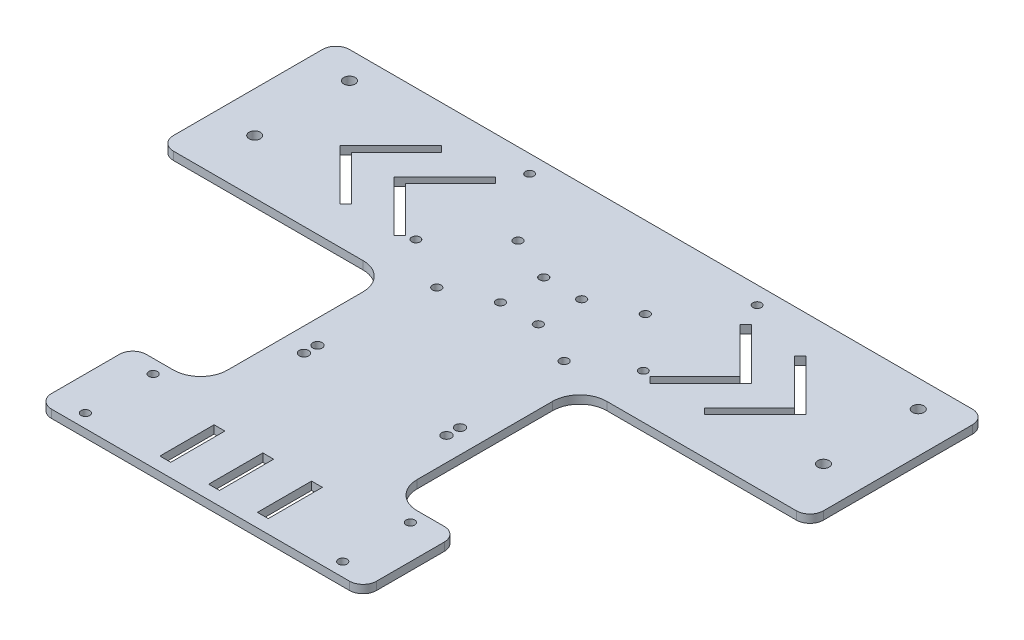
SolidWorks part; units mm, degrees
material "Thornel Mat VMA"
ref_plane "前视基准面" through (0, 0, 0) normal (0, 0, 1) x (1, 0, 0)
ref_plane "上视基准面" through (0, 0, 0) normal (0, 1, 0) x (1, 0, 0)
ref_plane "右视基准面" through (0, 0, 0) normal (1, 0, 0) x (0, 0, -1)
sketch "草图1" plane through (0, 0, 0) normal (0, 1, 0) x (1, 0, 0)
  line L0 (-105, 32.5) -> (-105, -32.5) construction
  line L1 (-120, -32.5) -> (120, -32.5)
  line L2 (-120, -32.5) -> (-120, 32.5)
  line L3 (-120, 32.5) -> (120, 32.5)
  line L4 (120, -32.5) -> (120, 32.5)
  line L5 (-120, -32.5) -> (120, 32.5) construction
  line L6 (-120, 32.5) -> (120, -32.5) construction
  line L7 (0, 32.5) -> (0, -32.5) construction
  line L8 (0, -82.5) -> (0, -32.5) construction
  line L9 (-60, -32.5) -> (20, -32.5)
  circle A0 centre (-105, 22.5) radius 2.1
  circle A1 centre (-105, -12.5) radius 2.1
  circle A2 centre (105, -12.5) radius 2.1
  circle A3 centre (105, 22.5) radius 2.1
  point P0 (0, 0)
  dimension "D4" = 20
  dimension "D5" = 35
  dimension "D1" = 65
  dimension "D2" = 240
  dimension "D3" = 15
extrude "凸台-拉伸1" add sketch "草图1" along normal blind 3 contours L1 L4 L3 L2 A2 A1 A0 A3 | L1 region at (0, 0, 0.0178)
sketch "草图3" plane through (0, 3, 0) normal (0, 1, 0) x (1, 0, 0)
  line L0 (0.7261, -44.1829) -> (0.7261, -109.1829) construction
  line L2 (-120, -32.5) -> (120, -32.5) construction
  line L3 (-40, -12.5) -> (40, -12.5) construction
  circle A0 centre (-22.7739, 2.5) radius 1.6
  circle A1 centre (24.2261, 2.5) radius 1.6
  circle A2 centre (24.2261, -27.5) radius 1.6
  circle A3 centre (-22.7739, -27.5) radius 1.6
  circle A4 centre (-6.2739, -4.5) radius 1.6
  circle A5 centre (7.7261, -4.5) radius 1.6
  circle A6 centre (7.7261, -20.5) radius 1.6
  circle A7 centre (-6.2739, -20.5) radius 1.6
  dimension "D1" = 3.2
  dimension "D2" = 47
  dimension "D3" = 30
  dimension "D4" = 14
  dimension "D5" = 16
  dimension "D6" = 5
extrude "切除-拉伸1" cut sketch "草图3" against normal through all
sketch "草图4" plane through (0, 0, 0) normal (0, 1, 0) x (1, 0, 0)
  line L0 (0, 32.5) -> (0, -113.7655) construction
  line L2 (-35, -32.5) -> (-35, -137.5)
  line L3 (-120, -32.5) -> (120, -32.5) construction
  line L4 (-35, -137.5) -> (35, -137.5)
  line L5 (35, -32.5) -> (35, -137.5)
  line L6 (-35, -32.5) -> (35, -32.5)
  line L7 (-35, -102.5) -> (-60, -102.5)
  line L8 (-60, -102.5) -> (-60, -137.5)
  line L9 (-60, -137.5) -> (-35, -137.5)
  line L10 (60, -102.5) -> (60, -137.5)
  line L11 (60, -137.5) -> (35, -137.5)
  line L12 (35, -102.5) -> (60, -102.5)
  point P9 (0, -137.5)
  dimension "D1" = 105
  dimension "D2" = 35
  dimension "D3" = 60
  dimension "D4" = 35
extrude "凸台-拉伸2" add sketch "草图4" along normal blind 3 contours L0 L6 L2 L4 | L6 L0 L4 L5 | L8 L9 L2 L7 | L12 L5 L11 L10 region at (-17.5, 0, 33.7619) region at (-47.5, 0, 120) region at (47.5, 0, 120)
fillet "圆角1" radius 10 2 edges at (35, 1.5, 32.5) (-35, 1.5, 32.5)
sketch "草图5" plane through (0, 3, 0) normal (0, 1, 0) x (1, 0, 0)
  line L0 (0, 32.5) -> (0, -137.5) construction
  line L1 (-120, 32.5) -> (120, 32.5) construction
  line L2 (-2, -112.5) -> (2, -112.5)
  line L3 (-120, -132.5) -> (120, -132.5) construction
  line L4 (-120, -32.5) -> (-120, 32.5) construction
  line L5 (120, -32.5) -> (120, 32.5) construction
  line L6 (-20, -112.5) -> (-16, -112.5)
  line L7 (-60, -137.5) -> (60, -137.5) construction
  line L8 (-20, -112.5) -> (-20, -132.5)
  line L9 (-20, -132.5) -> (-16, -132.5)
  line L10 (-16, -112.5) -> (-16, -132.5)
  line L11 (-2, -112.5) -> (-2, -132.5)
  line L12 (2, -112.5) -> (2, -132.5)
  line L13 (-2, -132.5) -> (2, -132.5)
  line L14 (16, -112.5) -> (20, -112.5)
  line L15 (16, -112.5) -> (16, -132.5)
  line L16 (20, -112.5) -> (20, -132.5)
  line L17 (16, -132.5) -> (20, -132.5)
  circle A0 centre (-47.5, -132.5) radius 1.6
  circle A1 centre (47.5, -132.5) radius 1.6
  circle A2 centre (-47.5, -107.5) radius 1.6
  circle A3 centre (47.5, -107.5) radius 1.6
  point P25 (-18, -112.5)
  point P33 (18, -112.5)
  dimension "D2" = 3.2
  dimension "D3" = 95
  dimension "D1" = 5
  dimension "D5" = 20
  dimension "D6" = 16
  dimension "D7" = 4
  dimension "D9" = 36
  dimension "D4" = 2
  dimension "D8" = 3
extrude "切除-拉伸2" cut sketch "草图5" against normal through all
fillet "圆角2" radius 10 2 edges at (35, 1.5, 102.5) (-35, 1.5, 102.5)
sketch "草图7" plane through (0, 3, 0) normal (0, 1, 0) x (1, 0, 0)
  line L0 (-120, 0) -> (120, 0) construction
  line L1 (-120, -32.5) -> (-120, 32.5) construction
  line L2 (120, -32.5) -> (120, 32.5) construction
  line L3 (0, 32.5) -> (0, -32.5) construction
  line L4 (-120, 32.5) -> (120, 32.5) construction
  line L5 (-105, 22.5) -> (-105, -12.5) construction
  line L6 (-22.7739, 2.5) -> (-22.7739, -27.5) construction
  line L7 (-22.7739, 2.5) -> (-105, 2.5) construction
  line L8 (-63.887, 2.5) -> (-63.887, 0) construction
  line L9 (-63.887, 0) -> (-46.2093, 17.6777)
  line L10 (-83.887, 0) -> (-66.2093, 17.6777)
  line L11 (-63.887, 0) -> (-46.2093, -17.6777)
  line L12 (-83.887, 0) -> (-66.2093, -17.6777)
  line L13 (83.887, 0) -> (66.2093, -17.6777)
  line L14 (63.887, 0) -> (46.2093, -17.6777)
  line L15 (63.887, 0) -> (46.2093, 17.6777)
  line L16 (83.887, 0) -> (66.2093, 17.6777)
  dimension "D1" = 25
  dimension "D2" = 45
  dimension "D3" = 2
extrude "切除-拉伸-薄壁1" cut sketch "草图7" against normal through all thin thin type mid plane wall 3
sketch "草图8" plane through (0, 3, 0) normal (0, 1, 0) x (1, 0, 0)
  line L0 (-35, -42.5) -> (35, -42.5) construction
  line L1 (35, -92.5) -> (-35, -92.5) construction
  line L2 (0, -42.5) -> (0, -92.5) construction
  line L3 (-35, -70.5) -> (35, -70.5) construction
  line L6 (-120, -32.5) -> (-45, -32.5) construction
  circle A0 centre (-26.3163, -68) radius 1.75
  circle A1 centre (-26.3163, -73) radius 1.75
  circle A2 centre (26.3163, -73) radius 1.75
  circle A3 centre (26.3163, -68) radius 1.75
  dimension "D1" = 3.5
  dimension "D2" = 5
  dimension "D3" = 38
extrude "切除-拉伸5" cut sketch "草图8" against normal through all
sketch "草图9" plane through (0, 3, 0) normal (0, 1, 0) x (1, 0, 0)
  line L0 (-105, 22.5) -> (-105, -12.5) construction
  line L1 (-105, -12.5) -> (105, -12.5) construction
  line L2 (-105, 5) -> (105, 5) construction
  line L3 (0, 26) -> (0, -16) construction
  line L4 (-42, -16) -> (42, -16) construction
  line L5 (-42, -16) -> (-42, 26) construction
  line L6 (-42, 26) -> (42, 26) construction
  line L7 (42, -16) -> (42, 26) construction
  line L8 (-42, -16) -> (42, 26) construction
  line L9 (-42, 26) -> (42, -16) construction
  circle A0 centre (-42, 26) radius 1.55
  circle A1 centre (-42, -16) radius 1.55
  circle A2 centre (42, -16) radius 1.55
  circle A3 centre (42, 26) radius 1.55
  point P8 (0, 5)
  dimension "D3" = 3.1
  dimension "D1" = 84
  dimension "D2" = 42
extrude "切除-拉伸6" cut sketch "草图9" against normal through all
fillet "圆角3" radius 5 8 edges at (-60, 1.5, 102.5) (-60, 1.5, 137.5) (60, 1.5, 102.5) (60, 1.5, 137.5) (120, 1.5, -32.5) (120, 1.5, 32.5) (-120, 1.5, 32.5) (-120, 1.5, -32.5)
